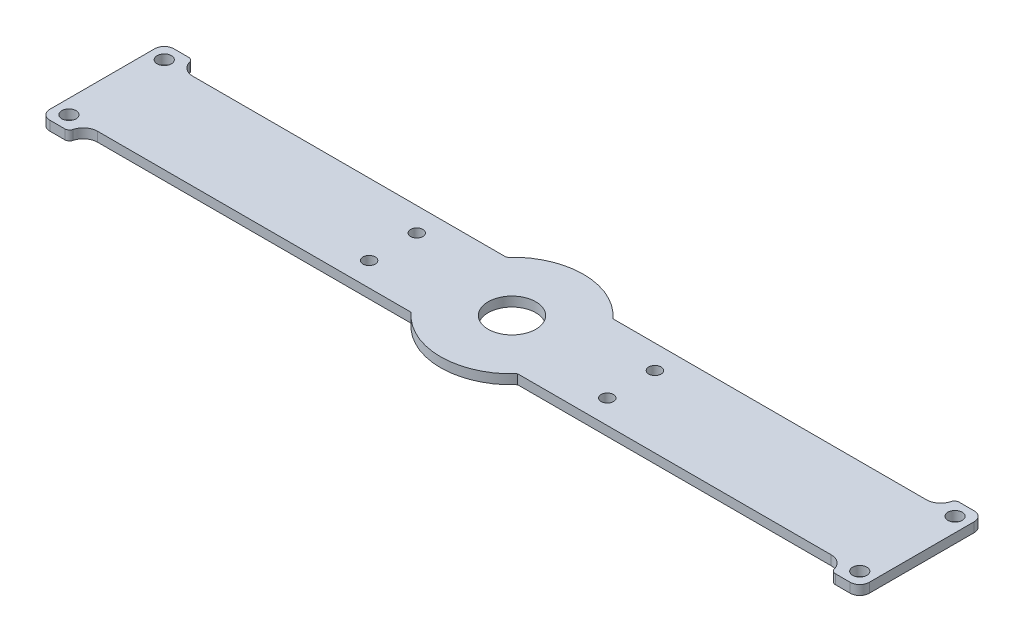
SolidWorks part; units mm, degrees
material "Thornel Mat VMA"
ref_plane "前视基准面" through (0, 0, 0) normal (0, 0, 1) x (1, 0, 0)
ref_plane "上视基准面" through (0, 0, 0) normal (0, 1, 0) x (1, 0, 0)
ref_plane "右视基准面" through (0, 0, 0) normal (1, 0, 0) x (0, 0, -1)
sketch "草图1" plane through (0, 0, 0) normal (0, 1, 0) x (1, 0, 0)
  line L0 (11.1803, 10) -> (80, 10)
  line L1 (-80, 10) -> (-11.1803, 10)
  line L2 (-80, 10) -> (-80, -10)
  line L3 (-80, -10) -> (-11.1803, -10)
  line L4 (80, 10) -> (80, -10)
  line L5 (0, -27.2578) -> (0, 34.9025) construction
  line L6 (-80, 0) -> (80, 0) construction
  line L7 (11.1803, -10) -> (80, -10)
  arc A0 (-11.1803, -10) -> (11.1803, -10) centre (0, 0) ccw
  arc A1 (11.1803, 10) -> (-11.1803, 10) centre (0, 0) ccw
  circle A2 centre (0, 0) radius 5
  dimension "D1" = 30
  dimension "D5" = 10
  dimension "D2" = 20
  dimension "D3" = 80
  dimension "D4" = 80
extrude "凸台-拉伸1" add sketch "草图1" along normal blind 2
sketch "草图2" plane through (0, 2, 0) normal (0, 1, 0) x (1, 0, 0)
  line L0 (-80, 0) -> (80, 0) construction
  line L1 (-80, 10) -> (-80, -10) construction
  line L2 (80, -10) -> (80, 10) construction
  line L3 (0, 15) -> (0, -15) construction
  arc A0 (11.1803, 10) -> (-11.1803, 10) centre (0, 0) ccw construction
  arc A1 (-11.1803, -10) -> (11.1803, -10) centre (0, 0) ccw construction
  circle A2 centre (-25, 5) radius 1.3
  circle A3 centre (-25, -5) radius 1.3
  circle A4 centre (25, -5) radius 1.3
  circle A5 centre (25, 5) radius 1.3
  dimension "D1" = 50
  dimension "D2" = 10
  dimension "D3" = 2.6
extrude "切除-拉伸1" cut sketch "草图2" against normal blind 2
sketch "草图3" plane through (0, 0, 0) normal (0, 1, 0) x (1, 0, 0)
  line L0 (0, 23.2514) -> (0, -27.1743) construction
  line L1 (-47.4426, 0) -> (47.933, 0) construction
  line L2 (-80, -13) -> (-80, 13)
  line L3 (-80, 10) -> (-80, -10) construction
  line L4 (-80, 13) -> (-86, 13)
  line L5 (-86, 13) -> (-86, -13)
  line L6 (-80, -13) -> (-86, -13)
  line L7 (80, -13) -> (86, -13)
  line L8 (86, 13) -> (86, -13)
  line L9 (80, 13) -> (86, 13)
  line L10 (80, -13) -> (80, 13)
  line L11 (-83, 13) -> (-83, -13) construction
  line L12 (83, 13) -> (83, -13) construction
  circle A0 centre (-83, 10) radius 1.5
  circle A1 centre (-83, -10) radius 1.5
  circle A2 centre (83, -10) radius 1.5
  circle A3 centre (83, 10) radius 1.5
  point P12 (-80, 0)
  point P13 (-86, 0)
  dimension "D3" = 3
  dimension "D4" = 20
  dimension "D1" = 6
  dimension "D2" = 26
extrude "凸台-拉伸2" add sketch "草图3" along normal blind 2
fillet "圆角1" radius 3 4 edges at (80, 1, 10) (80, 1, -10) (-80, 1, -10) (-80, 1, 10)
fillet "圆角2" radius 2 4 edges at (-86, 1, -13) (-86, 1, 13) (86, 1, 13) (86, 1, -13)
fillet "圆角3" radius 1 4 edges at (80, 1, 13) (80, 1, -13) (-80, 1, 13) (-80, 1, -13)
